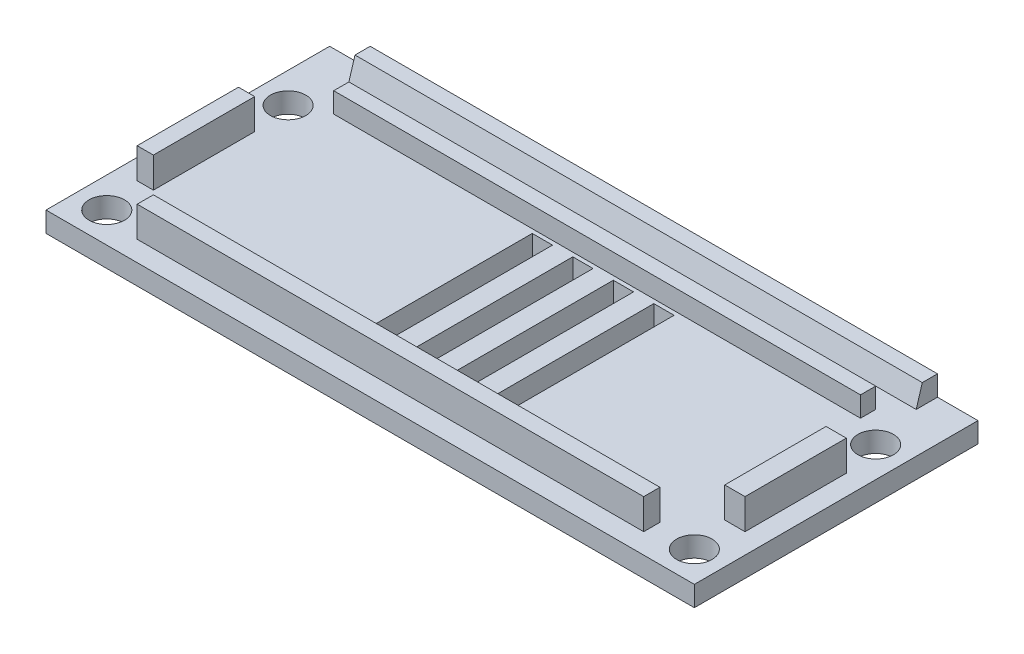
SolidWorks part; units mm, degrees
material "PET"
ref_plane "Ebene vorne" through (0, 0, 0) normal (0, 0, 1) x (1, 0, 0)
ref_plane "Ebene oben" through (0, 0, 0) normal (0, 1, 0) x (1, 0, 0)
ref_plane "Ebene rechts" through (0, 0, 0) normal (1, 0, 0) x (0, 0, -1)
sketch "Skizze1" plane through (0, 0, 0) normal (0, 1, 0) x (1, 0, 0)
  line L1 (0, 0) -> (64, 0)
  line L2 (0, 0) -> (0, 28)
  line L3 (0, 28) -> (64, 28)
  line L4 (64, 0) -> (64, 28)
  dimension "D1" = 28
  dimension "D2" = 64
extrude "Aufsatz-Linear austragen1" add sketch "Skizze1" along normal blind 2
sketch "Skizze2" plane through (0, 2, 0) normal (0, 1, 0) x (1, 0, 0)
  line L0 (0, 28) -> (0, 0) construction
  line L1 (0, 0) -> (64, 0) construction
  line L2 (64, 0) -> (64, 28) construction
  circle A0 centre (3, 3) radius 1.75
  circle A1 centre (3, 20.9) radius 1.75
  circle A4 centre (61, 20.9) radius 1.75
  circle A5 centre (61, 3) radius 1.75
  dimension "D1" = 3.5
  dimension "D2" = 3
  dimension "D3" = 3
  dimension "D4" = 3
  dimension "D5" = 3
  dimension "D6" = 17.9
extrude "Schnitt-Linear austragen1" cut sketch "Skizze2" against normal through all
sketch "Skizze3" plane through (0, 2, 0) normal (0, 1, 0) x (1, 0, 0)
  line L0 (0, 0) -> (64, 0) construction
  line L1 (26, 22) -> (28, 22)
  line L2 (26, 22) -> (26, 6)
  line L3 (26, 6) -> (28, 6)
  line L4 (28, 22) -> (28, 6)
  line L5 (0, 28) -> (0, 0) construction
  dimension "D1" = 2
  dimension "D2" = 16
  dimension "D3" = 6
  dimension "D4" = 26
extrude "Schnitt-Linear austragen2" cut sketch "Skizze3" against normal through all
pattern_linear "Lineares Muster1" count 4 spacing 4 along (1, 0, 0) of "Schnitt-Linear austragen2"
sketch "Skizze5" plane through (0, 2, 0) normal (0, 1, 0) x (1, 0, 0)
  line L0 (0, 0) -> (64, 0) construction
  line L1 (2, 17) -> (3.6, 17)
  line L2 (2, 17) -> (2, 7)
  line L3 (2, 7) -> (3.6, 7)
  line L4 (3.6, 17) -> (3.6, 7)
  line L5 (7, 3.6) -> (57, 3.6)
  line L6 (7, 3.6) -> (7, 2)
  line L7 (7, 2) -> (57, 2)
  line L8 (57, 3.6) -> (57, 2)
  line L13 (60, 17) -> (62, 17)
  line L14 (60, 17) -> (60, 7)
  line L15 (60, 7) -> (62, 7)
  line L16 (62, 17) -> (62, 7)
  line L17 (0, 28) -> (0, 0) construction
  line L18 (64, 0) -> (64, 28) construction
  dimension "D1" = 10
  dimension "D2" = 1.6
  dimension "D3" = 7
  dimension "D4" = 7
  dimension "D5" = 2
  dimension "D6" = 2
  dimension "D7" = 2
  dimension "D8" = 2
  dimension "D9" = 2
  dimension "D10" = 7
extrude "Aufsatz-Linear austragen2" add sketch "Skizze5" along normal blind 3
sketch "Skizze6" plane through (0, 2, 0) normal (0, 1, 0) x (1, 0, 0)
  line L0 (0, 28) -> (0, 0) construction
  line L1 (6, 22.4) -> (58, 22.4)
  line L2 (6, 22.4) -> (6, 23.9)
  line L3 (6, 23.9) -> (58, 23.9)
  line L4 (58, 22.4) -> (58, 23.9)
  line L11 (64, 0) -> (64, 28) construction
  line L12 (64, 28) -> (0, 28) construction
  dimension "D1" = 6
  dimension "D2" = 1.5
  dimension "D3" = 6
  dimension "D4" = 4.1
extrude "Aufsatz-Linear austragen3" add sketch "Skizze6" along normal blind 2
sketch "Skizze7" plane through (0, 2, 0) normal (0, 1, 0) x (1, 0, 0)
  line L0 (64, 28) -> (0, 28) construction
  line L1 (4, 28) -> (60, 28)
  line L2 (4, 28) -> (4, 25.9)
  line L3 (4, 25.9) -> (60, 25.9)
  line L4 (60, 28) -> (60, 25.9)
  line L5 (0, 28) -> (0, 0) construction
  dimension "D1" = 2.1
  dimension "D2" = 56
  dimension "D3" = 4
extrude "Aufsatz-Linear austragen4" add sketch "Skizze7" along normal blind 2
chamfer "Fase1" distance 2 distance2 0.6 1 edges at (32, 4, -25.9) first distance on face at (32, 3, -25.9)
